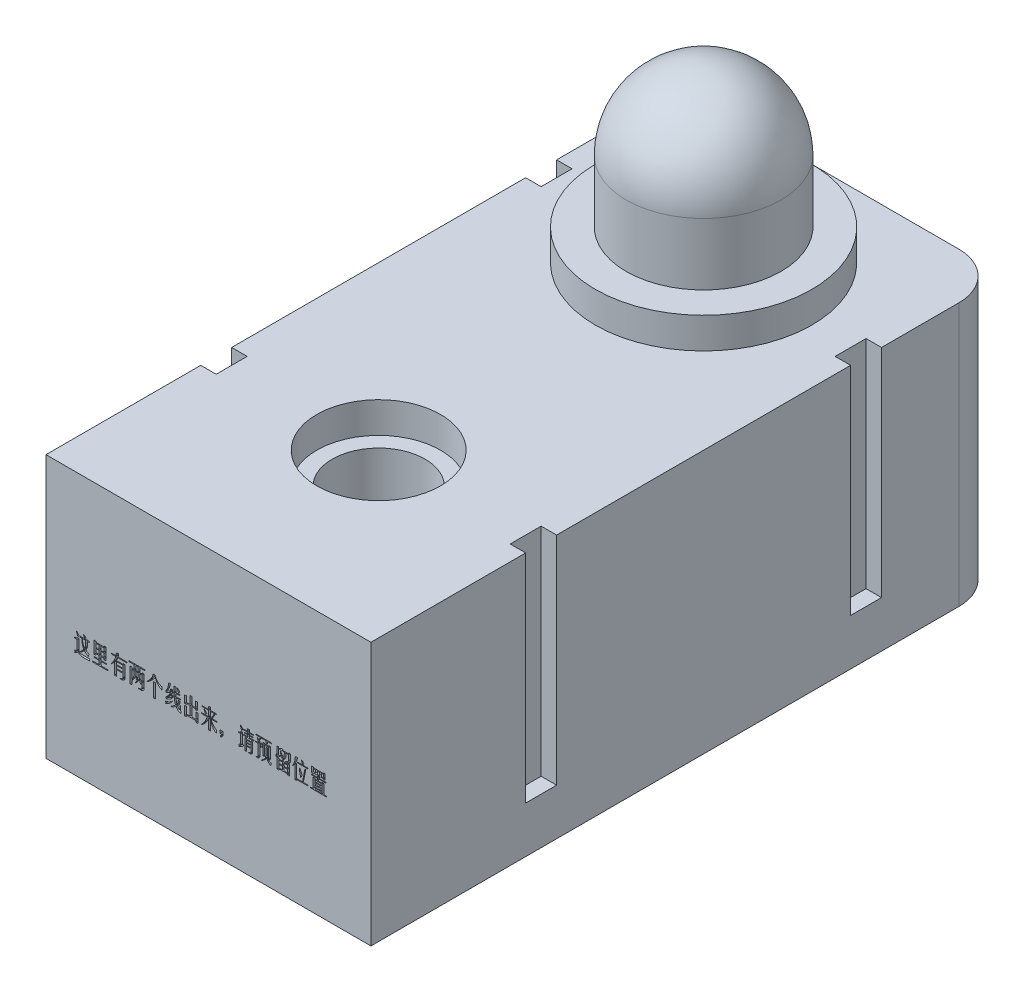
SolidWorks part; units mm, degrees
ref_plane "前视基准面" through (0, 0, 0) normal (0, 0, 1) x (1, 0, 0)
ref_plane "上视基准面" through (0, 0, 0) normal (0, 1, 0) x (1, 0, 0)
ref_plane "右视基准面" through (0, 0, 0) normal (1, 0, 0) x (0, 0, -1)
other "Configuration Table"
sketch "草图1" plane through (0, 0, 0) normal (0, 1, 0) x (1, 0, 0)
  line L0 (5.25, 0) -> (5.25, -20.5) construction
  line L1 (0, 0) -> (10.5, 0)
  line L2 (0, 0) -> (0, -20.5)
  line L3 (0, -20.5) -> (10.5, -20.5)
  line L4 (10.5, 0) -> (10.5, -20.5)
  line L5 (0, -15) -> (10.5, -15) construction
  line L6 (0, -4.5) -> (10.5, -4.5) construction
  line L8 (10, -14.5) -> (11, -14.5)
  line L9 (10, -14.5) -> (10, -15.5)
  line L10 (10, -15.5) -> (11, -15.5)
  line L11 (11, -14.5) -> (11, -15.5)
  line L12 (10, -14.5) -> (11, -15.5) construction
  line L13 (10, -15.5) -> (11, -14.5) construction
  line L14 (-0.5, -14.5) -> (0.5, -14.5)
  line L15 (-0.5, -14.5) -> (-0.5, -15.5)
  line L16 (-0.5, -15.5) -> (0.5, -15.5)
  line L17 (0.5, -14.5) -> (0.5, -15.5)
  line L18 (-0.5, -14.5) -> (0.5, -15.5) construction
  line L19 (-0.5, -15.5) -> (0.5, -14.5) construction
  line L20 (-0.5, -4) -> (0.5, -4)
  line L21 (-0.5, -4) -> (-0.5, -5)
  line L22 (-0.5, -5) -> (0.5, -5)
  line L23 (0.5, -4) -> (0.5, -5)
  line L24 (-0.5, -4) -> (0.5, -5) construction
  line L25 (-0.5, -5) -> (0.5, -4) construction
  line L26 (11, -4) -> (10, -4)
  line L27 (11, -4) -> (11, -5)
  line L28 (11, -5) -> (10, -5)
  line L29 (10, -4) -> (10, -5)
  line L30 (11, -4) -> (10, -5) construction
  line L31 (11, -5) -> (10, -4) construction
  circle A0 centre (5.25, -15) radius 1.5
  circle A1 centre (5.25, -4.5) radius 3.5
  circle A2 centre (5.25, -4.5) radius 2.5
  dimension "D3" = 3
  dimension "D4" = 5.5
  dimension "D5" = 7
  dimension "D6" = 4.5
  dimension "D7" = 5
  dimension "D1" = 20.5
  dimension "D2" = 10.5
  dimension "D8" = 1
  dimension "D9" = 1
  dimension "D10" = 1
  dimension "D11" = 1
  dimension "D12" = 1
  dimension "D13" = 1
  dimension "D14" = 1
  dimension "D15" = 1
extrude "凸台-拉伸1" add sketch "草图1" along normal blind 1.5 contours L29 L26 L4 L1 L2 L20 L23 L22 L14 L17 L16 L3 L10 L9 L8 L28 A1 A0 | L17 L14 L2 L16 | L23 L20 L2 L22 | A1 A2 | A2 | L26 L29 L28 L4 | L9 L10 L4 L8 region at (5.25, 0, 11.3753) region at (0.25, 0, 4.5) region at (10.25, 0, 4.5) region at (0.25, 0, 15) region at (10.25, 0, 15) region at (1.849, 0, 4.5) region at (5.25, 0, 4.5)
extrude "凸台-拉伸2" add sketch "草图1<3>" along normal blind 8.5 contours L29 L26 L4 L1 L2 L20 L23 L22 L14 L17 L16 L3 L10 L9 L8 L28 A1 A0 | A1 A2 | A2 region at (5.25, 0, 11.3753) region at (1.849, 0, 4.5) region at (5.25, 0, 4.5)
sketch "草图1<3>" plane through (0, 0, 0) normal (0, 1, 0) x (1, 0, 0) same geometry as "草图1"
extrude "凸台-拉伸3" add sketch "草图1<5>" along normal blind 9.5 contours A1 A2 | A2 region at (1.849, 0, 4.5) region at (5.25, 0, 4.5)
sketch "草图1<5>" plane through (0, 0, 0) normal (0, 1, 0) x (1, 0, 0) same geometry as "草图1"
extrude "凸台-拉伸4" add sketch "草图1<6>" along normal blind 14 contours A2 region at (5.25, 0, 4.5)
sketch "草图1<6>" plane through (0, 0, 0) normal (0, 1, 0) x (1, 0, 0) same geometry as "草图1"
fillet "圆角1" radius 2.5 1 edges at (5.25, 14, 7)
sketch "草图2" plane through (0, 8.5, 0) normal (0, 1, 0) x (1, 0, 0)
  circle A0 centre (5.25, -15) radius 2
  dimension "D1" = 4
extrude "切除-拉伸1" cut sketch "草图2" against normal blind 1
fillet "圆角2" radius 1.5 2 edges at (10.5, 4.25, 0) (0, 4.25, 0)
sketch "草图3" plane through (0, 0, 20.5) normal (0, 0, 1) x (1, 0, 0)
  text T0 "这里有两个线出来，请预留位置" font "方正姚体" height 0.5158
extrude "切除-拉伸2" cut sketch "草图3" against normal blind 0.1
